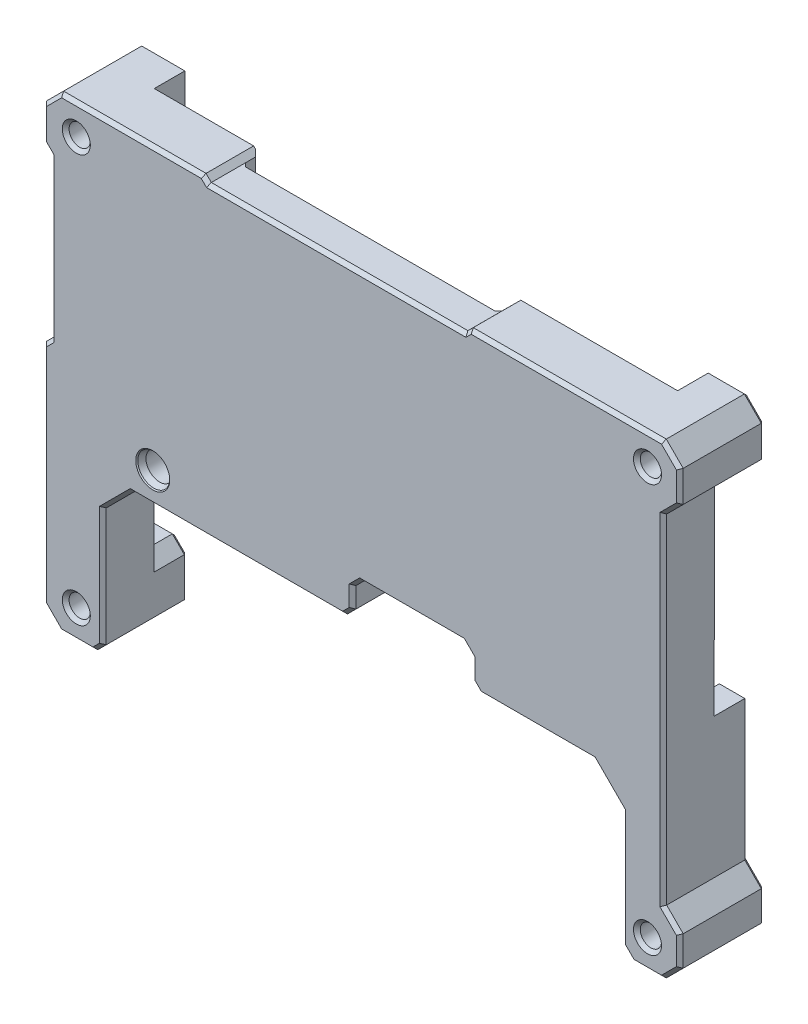
SolidWorks part; units mm, degrees
ref_plane "前视基准面" through (0, 0, 0) normal (0, 0, 1) x (1, 0, 0)
ref_plane "上视基准面" through (0, 0, 0) normal (0, 1, 0) x (1, 0, 0)
ref_plane "右视基准面" through (0, 0, 0) normal (1, 0, 0) x (0, 0, -1)
other "Configuration Table"
sketch "草图1" plane through (0, 0, 0) normal (0, 0, 1) x (1, 0, 0)
  line L1 (0, 0) -> (85, 0)
  line L2 (0, 0) -> (0, 65)
  line L3 (0, 65) -> (85, 65)
  line L4 (85, 0) -> (85, 65)
  dimension "D1" = 65
  dimension "D2" = 85
extrude "凸台-拉伸1" add sketch "草图1" along normal blind 10
sketch "草图2" plane through (0, 0, 0) normal (0, 0, -1) x (-1, 0, 0)
  circle A0 centre (-76.1669, 56.4425) radius 1.25
  circle A1 centre (-8.8888, 56.4425) radius 1.25
  circle A2 centre (-76.1669, 8.4151) radius 1.25
  circle A3 centre (-8.8888, 8.4151) radius 1.25
  dimension "D1" = 2.5
  dimension "D2" = 2.5
  dimension "D3" = 2.5
  dimension "D4" = 2.5
extrude "切除-拉伸1" cut sketch "草图2" against normal up to next
sketch "草图3" plane through (0, 0, 0) normal (0, 0, -1) x (-1, 0, 0)
  line L28 (-85, 0) -> (-85, 65) construction
  line L29 (-85, 65) -> (0, 65)
  line L30 (-85, 65) -> (-85, 0)
  line L31 (-85, 0) -> (0, 0)
  line L32 (0, 65) -> (0, 0)
  line L56 (-5, 33.4629) -> (-5.8713, 34.3342)
  line L57 (-5, 6.9926) -> (-5, 33.4629)
  line L58 (-6.9926, 5) -> (-5, 6.9926)
  line L59 (-16.2697, 5) -> (-6.9926, 5)
  line L60 (-17.4616, 6.1866) -> (-16.2697, 5)
  line L61 (-31.7436, 6.1829) -> (-17.4616, 6.1866)
  line L62 (-32.9265, 5) -> (-31.7436, 6.1829)
  line L63 (-58.7727, 5) -> (-32.9265, 5)
  line L64 (-60.0435, 6.2655) -> (-58.7727, 5)
  line L65 (-73.1524, 6.2618) -> (-60.0435, 6.2655)
  line L66 (-74.4142, 5) -> (-73.1524, 6.2618)
  line L67 (-77.9822, 5) -> (-74.4142, 5)
  line L68 (-79.9747, 6.9926) -> (-77.9822, 5)
  line L69 (-79.9747, 10.5083) -> (-79.9747, 6.9926)
  line L70 (-78.0283, 12.46) -> (-79.9747, 10.5083)
  line L71 (-78.032, 52.3531) -> (-78.0283, 12.46)
  line L72 (-79.9747, 54.2958) -> (-78.032, 52.3531)
  line L73 (-79.9747, 57.9821) -> (-79.9747, 54.2958)
  line L74 (-77.9822, 59.9747) -> (-79.9747, 57.9821)
  line L75 (-55.2451, 59.9747) -> (-77.9822, 59.9747)
  line L76 (-54.6148, 59.3497) -> (-55.2451, 59.9747)
  line L77 (-24.3949, 59.3534) -> (-54.6148, 59.3497)
  line L78 (-23.7736, 59.9747) -> (-24.3949, 59.3534)
  line L79 (-6.9926, 59.9747) -> (-23.7736, 59.9747)
  line L80 (-5, 57.9821) -> (-6.9926, 59.9747)
  line L81 (-5, 54.0174) -> (-5, 57.9821)
  line L82 (-5.875, 53.1371) -> (-5, 54.0174)
  line L83 (-5.8713, 34.3342) -> (-5.875, 53.1371)
extrude "切除-拉伸2" cut sketch "草图3" against normal up to next
sketch "草图4" plane through (0, 0, 0) normal (0, 0, -1) x (-1, 0, 0)
  line L0 (-73.1524, 6.2618) -> (-73.1524, 20.0323)
  line L1 (-73.1524, 20.0323) -> (-69.8316, 23.3532)
  line L2 (-69.8316, 23.3532) -> (-46.788, 23.3532)
  line L3 (-46.788, 23.3532) -> (-15.4038, 23.3532)
  line L4 (-15.4038, 23.3532) -> (-12.014, 19.9634)
  line L5 (-12.014, 19.9634) -> (-12.014, 6.188)
  line L6 (-31.7436, 6.1829) -> (-17.4616, 6.1866) construction
  line L7 (-12.014, 6.188) -> (-12.014, 0.194)
  line L8 (-12.014, 0.194) -> (-73.1524, 0.194)
  line L9 (-73.1524, 0.194) -> (-73.1524, 6.2618)
  line L10 (-73.1524, 6.2618) -> (-60.0435, 6.2655) construction
  dimension "D1" = 135
  dimension "D2" = 135
  dimension "D3" = 4.7938
extrude "切除-拉伸4" cut sketch "草图4" against normal up to next
sketch "草图5" plane through (0, 0, 0) normal (0, 0, -1) x (-1, 0, 0)
  line L0 (-24.3949, 59.3534) -> (-24.3949, 53.9064)
  line L1 (-24.3949, 53.9064) -> (-25.5261, 52.7749)
  line L2 (-25.5261, 52.7749) -> (-53.4826, 52.7749)
  line L3 (-53.4826, 52.7749) -> (-54.6142, 53.9061)
  line L4 (-54.6142, 53.9061) -> (-54.6148, 59.3497)
  line L5 (-24.3949, 59.3534) -> (-54.6148, 59.3497) construction
  line L6 (-23.7736, 59.9747) -> (-24.3949, 59.3534) construction
  line L7 (-24.3949, 59.3534) -> (-54.6148, 59.3497)
  dimension "D1" = 135
  dimension "D2" = 134.993
  dimension "D3" = 1.6
  dimension "D4" = 1.6
extrude "切除-拉伸7" cut sketch "草图5" against normal blind 6
sketch "草图6" plane through (0, 0, 0) normal (0, 0, -1) x (-1, 0, 0)
  line L0 (-5.8713, 34.3342) -> (-11.6713, 34.3342)
  line L1 (-5, 33.4629) -> (-5.8713, 34.3342) construction
  line L6 (-5.8713, 34.3342) -> (-5.875, 53.1371) construction
  line L7 (-5.8735, 45.2504) -> (-5.8745, 50.3342)
  line L8 (-5.8735, 45.2504) -> (-5.8713, 34.3342)
  line L9 (-5.8745, 50.3342) -> (-11.6713, 50.3342)
  line L10 (-11.6713, 50.3342) -> (-11.6713, 34.3342)
  dimension "D1" = 5.8
  dimension "D2" = 16
extrude "切除-拉伸8" cut sketch "草图6" against normal blind 6
sketch "草图7" plane through (0, 0, 0) normal (0, 0, -1) x (-1, 0, 0)
  line L0 (-76.4321, 51.2623) -> (-74.4321, 51.2623)
  line L1 (-74.4321, 51.2623) -> (-71.3195, 54.3749)
  line L2 (-71.3195, 54.3749) -> (-71.3195, 58.3749)
  line L3 (-71.3195, 58.3749) -> (-71.3195, 59.9747)
  line L4 (-76.4321, 51.2623) -> (-78.0319, 51.2623)
  line L5 (-78.0298, 28.9377) -> (-75.0298, 28.9377)
  line L6 (-75.0298, 28.9377) -> (-75.0298, 13.9377)
  line L7 (-72.9158, 11.8236) -> (-75.0298, 13.9377)
  line L8 (-24.3949, 57.6633) -> (-23.7321, 57.6633)
  line L9 (-23.7321, 57.6633) -> (-23.0617, 58.334)
  line L10 (-23.0617, 58.334) -> (-12.072, 58.334)
  line L11 (-12.072, 58.334) -> (-12.072, 55.334)
  line L12 (-12.072, 55.334) -> (-9.875, 53.1371)
  line L13 (-9.875, 53.1371) -> (-5.875, 53.1371)
  line L14 (-6.5998, 12.014) -> (-10.5998, 12.014)
  line L15 (-10.5998, 12.014) -> (-12.014, 10.5998)
  line L16 (-12.014, 10.5998) -> (-12.014, 5)
  line L17 (-6.5998, 12.014) -> (-5, 12.014)
  line L18 (-72.9158, 11.8236) -> (-73.1524, 12.0603)
  line L37 (-5.8713, 34.3342) -> (-11.6713, 34.3342)
  line L38 (-11.6713, 34.3342) -> (-11.6713, 50.3342)
  line L39 (-11.6713, 34.3342) -> (-11.6713, 50.3342)
  line L40 (-11.6713, 50.3342) -> (-5.8745, 50.3342)
  line L41 (-11.6713, 50.3342) -> (-5.8745, 50.3342)
  line L42 (-5.8745, 50.3342) -> (-5.875, 53.1371)
  line L43 (-5.875, 53.1371) -> (-5, 54.0174)
  line L44 (-5, 54.0174) -> (-5, 57.9821)
  line L45 (-5, 57.9821) -> (-6.9926, 59.9747)
  line L46 (-6.9926, 59.9747) -> (-23.7736, 59.9747)
  line L47 (-23.7736, 59.9747) -> (-24.3949, 59.3534)
  line L48 (-24.3949, 59.3534) -> (-24.3949, 53.9064)
  line L49 (-24.3949, 53.9064) -> (-25.5261, 52.7749)
  line L50 (-25.5261, 52.7749) -> (-53.4826, 52.7749)
  line L51 (-53.4826, 52.7749) -> (-54.6142, 53.9061)
  line L52 (-54.6142, 53.9061) -> (-54.6148, 59.3497)
  line L53 (-54.6148, 59.3497) -> (-55.2451, 59.9747)
  line L54 (-55.2451, 59.9747) -> (-77.9822, 59.9747)
  line L55 (-77.9822, 59.9747) -> (-79.9747, 57.9821)
  line L56 (-79.9747, 57.9821) -> (-79.9747, 54.2958)
  line L57 (-79.9747, 54.2958) -> (-78.032, 52.3531)
  line L58 (-78.032, 52.3531) -> (-78.0283, 12.46)
  line L59 (-78.0283, 12.46) -> (-79.9747, 10.5083)
  line L60 (-79.9747, 10.5083) -> (-79.9747, 6.9926)
  line L61 (-79.9747, 6.9926) -> (-77.9822, 5)
  line L62 (-77.9822, 5) -> (-74.4142, 5)
  line L63 (-74.4142, 5) -> (-73.1524, 6.2618)
  line L64 (-73.1524, 6.2618) -> (-73.1524, 20.0323)
  line L65 (-73.1524, 20.0323) -> (-69.8316, 23.3532)
  line L66 (-69.8316, 23.3532) -> (-15.4038, 23.3532)
  line L67 (-15.4038, 23.3532) -> (-12.014, 19.9634)
  line L68 (-12.014, 19.9634) -> (-12.014, 5)
  line L70 (-12.014, 5) -> (-6.9926, 5)
  line L71 (-6.9926, 5) -> (-5, 6.9926)
  line L72 (-5, 6.9926) -> (-5, 33.4629)
  line L73 (-5, 33.4629) -> (-5.8713, 34.3342)
  line L74 (-5.8713, 34.3342) -> (-11.6713, 34.3342)
  line L79 (-5.8745, 50.3342) -> (-5.875, 53.1371)
  line L80 (-5.875, 53.1371) -> (-5, 54.0174)
  line L81 (-5, 54.0174) -> (-5, 57.9821)
  line L82 (-5, 57.9821) -> (-6.9926, 59.9747)
  line L83 (-6.9926, 59.9747) -> (-23.7736, 59.9747)
  line L84 (-23.7736, 59.9747) -> (-24.3949, 59.3534)
  line L85 (-24.3949, 59.3534) -> (-24.3949, 53.9064)
  line L86 (-24.3949, 53.9064) -> (-25.5261, 52.7749)
  line L87 (-25.5261, 52.7749) -> (-53.4826, 52.7749)
  line L88 (-53.4826, 52.7749) -> (-54.6142, 53.9061)
  line L89 (-54.6142, 53.9061) -> (-54.6148, 59.3497)
  line L90 (-54.6148, 59.3497) -> (-55.2451, 59.9747)
  line L91 (-55.2451, 59.9747) -> (-77.9822, 59.9747)
  line L92 (-77.9822, 59.9747) -> (-79.9747, 57.9821)
  line L93 (-79.9747, 57.9821) -> (-79.9747, 54.2958)
  line L94 (-79.9747, 54.2958) -> (-78.032, 52.3531)
  line L95 (-78.032, 52.3531) -> (-78.0283, 12.46)
  line L96 (-78.0283, 12.46) -> (-79.9747, 10.5083)
  line L97 (-79.9747, 10.5083) -> (-79.9747, 6.9926)
  line L98 (-79.9747, 6.9926) -> (-77.9822, 5)
  line L99 (-77.9822, 5) -> (-74.4142, 5)
  line L100 (-74.4142, 5) -> (-73.1524, 6.2618)
  line L101 (-73.1524, 6.2618) -> (-73.1524, 20.0323)
  line L102 (-73.1524, 20.0323) -> (-69.8316, 23.3532)
  line L103 (-69.8316, 23.3532) -> (-15.4038, 23.3532)
  line L104 (-15.4038, 23.3532) -> (-12.014, 19.9634)
  line L105 (-12.014, 19.9634) -> (-12.014, 5)
  line L107 (-12.014, 5) -> (-6.9926, 5)
  line L108 (-6.9926, 5) -> (-5, 6.9926)
  line L109 (-5, 6.9926) -> (-5, 33.4629)
  line L110 (-5, 33.4629) -> (-5.8713, 34.3342)
  dimension "D2" = 90
  dimension "D3" = 15
  dimension "D4" = 135
  dimension "D5" = 4
  dimension "D6" = 3
  dimension "D7" = 135
  dimension "D8" = 45
  dimension "D9" = 3
  dimension "D1" = 0
extrude "切除-拉伸11" cut sketch "草图7" against normal blind 4
sketch "草图8" plane through (0, 0, 4) normal (0, 0, -1) x (-1, 0, 0)
  line L1 (-73.3481, 45.9587) -> (-65.3481, 45.9587)
  line L2 (-73.3481, 45.9587) -> (-73.3481, 40.9587)
  line L3 (-73.3481, 40.9587) -> (-65.3481, 40.9587)
  line L4 (-65.3481, 45.9587) -> (-65.3481, 40.9587)
  dimension "D1" = 5
  dimension "D2" = 8
extrude "切除-拉伸12" cut sketch "草图8" against normal blind 1
sketch "草图10" plane through (0, 0, 4) normal (0, 0, -1) x (-1, 0, 0)
  line L0 (-41.5465, 34.8898) -> (-37.5465, 34.8898)
  line L1 (-46.9465, 34.8898) -> (-41.5465, 34.8898)
  line L2 (-46.9465, 34.8898) -> (-46.9465, 28.8898)
  line L3 (-46.9465, 28.8898) -> (-41.5465, 28.8898)
  line L4 (-41.5465, 34.8898) -> (-41.5465, 28.8898)
  line L5 (-37.5465, 34.8898) -> (-32.1465, 34.8898)
  line L6 (-37.5465, 34.8898) -> (-37.5465, 28.8898)
  line L7 (-37.5465, 28.8898) -> (-32.1465, 28.8898)
  line L8 (-32.1465, 34.8898) -> (-32.1465, 28.8898)
  line L9 (-37.5465, 28.8898) -> (-41.5465, 28.8898)
  dimension "D1" = 5.4
  dimension "D2" = 6
  dimension "D3" = 5.4
  dimension "D4" = 4
extrude "凸台-拉伸2" add sketch "草图10" along normal offset from surface (2.04 mm away) 3 contours L4 L1 L2 L3 | L9 L6 L0 L4 | L8 L5 L6 L7
sketch "草图11" plane through (0, 0, 4) normal (0, 0, -1) x (-1, 0, 0)
  line L1 (-40.8318, 43.6929) -> (-36.6318, 43.6929)
  line L2 (-40.8318, 43.6929) -> (-40.8318, 38.6929)
  line L3 (-40.8318, 38.6929) -> (-36.6318, 38.6929)
  line L4 (-36.6318, 43.6929) -> (-36.6318, 38.6929)
  dimension "D1" = 4.2
  dimension "D2" = 5
extrude "凸台-拉伸3" add sketch "草图11" along normal offset from surface (1.3001 mm away) 3
sketch "草图12" plane through (0, 0, 4) normal (0, 0, -1) x (-1, 0, 0)
  line L0 (-24.6106, 30.6859) -> (-32.1465, 34.8898)
  line L1 (-30.6106, 30.6859) -> (-18.6106, 30.6859)
  line L2 (-30.6106, 30.6859) -> (-30.6106, 24.6859)
  line L3 (-30.6106, 24.6859) -> (-18.6106, 24.6859)
  line L4 (-18.6106, 30.6859) -> (-18.6106, 24.6859)
  line L5 (-32.1465, 34.8898) -> (-46.9465, 34.8898) construction
  line L6 (-32.1465, 28.8898) -> (-32.1465, 34.8898) construction
  line L7 (-32.1465, 34.8898) -> (-32.1465, 28.8898)
  line L8 (-32.1465, 28.8898) -> (-30.6106, 27.6859)
  line M47 (-32.1465, 34.8898) -> (-32.1465, 28.8898)
  dimension "D1" = 12
  dimension "D2" = 6
extrude "凸台-拉伸4" add sketch "草图12" along normal offset from surface (1.89 mm away) 3 contours L4 L1 L2 L3 | L8 L2 L1 L0 M47
sketch "草图13" plane through (0, 0, 4) normal (0, 0, -1) x (-1, 0, 0)
  line L1 (-62.8902, 40.6188) -> (-59.7758, 40.6188)
  line L2 (-62.8902, 40.6188) -> (-62.8902, 35.6362)
  line L3 (-62.8902, 35.6362) -> (-59.7758, 35.6362)
  line L4 (-59.7758, 40.6188) -> (-59.7758, 35.6362)
extrude "凸台-拉伸5" add sketch "草图13" along normal offset from surface (4 mm away) 2
sketch "草图15" plane through (0, 0, 10) normal (0, 0, 1) x (1, 0, 0)
  line L0 (69.8316, 23.3532) -> (15.4038, 23.3532) construction
  line L1 (41.4288, 23.3532) -> (55.4288, 23.3532)
  line L2 (41.4288, 23.3532) -> (41.4288, 27.7532)
  line L3 (41.4288, 27.7532) -> (55.4288, 27.7532)
  line L4 (55.4288, 23.3532) -> (55.4288, 27.7532)
  dimension "D1" = 14
  dimension "D2" = 4.4
extrude "切除-拉伸13" cut sketch "草图15" against normal up to surface (6 mm away) up to face at (69.3481, 43.4587, 4)
chamfer "倒角1" distance 1 angle 45 5 edges at (12.014, 5, 5) (55.4288, 23.3532, 7) (55.4288, 27.7532, 7) (41.4288, 27.7532, 7) (41.4288, 23.3532, 7)
chamfer "倒角2" distance 0.6 angle 45 4 edges at (59.7758, 38.1275, 4) (61.333, 40.6188, 4) (62.8902, 38.1275, 4) (61.333, 35.6362, 4)
chamfer "倒角5" distance 0.6 angle 45 4 edges at (36.6318, 41.1929, 4) (38.7318, 38.6929, 4) (40.8318, 41.1929, 4) (38.7318, 43.6929, 4)
sketch "草图16" plane through (0, 0, 4) normal (0, 0, -1) x (-1, 0, 0)
  circle A0 centre (-17.8941, 26.9463) radius 1.6
  dimension "D1" = 3.2
extrude "切除-拉伸14" cut sketch "草图16" against normal through all both and the other way through all
sketch "草图17" plane through (0, 0, 0) normal (0, 0, -1) x (-1, 0, 0)
  line L0 (-12.072, 58.334) -> (-12.072, 59.9747)
  line L2 (-6.9926, 59.9747) -> (-23.7736, 59.9747) construction
  line L15 (-24.3949, 59.3534) -> (-24.3949, 57.6633)
  line L16 (-24.3949, 57.6633) -> (-23.7321, 57.6633)
  line L17 (-23.7321, 57.6633) -> (-23.0617, 58.334)
  line L18 (-23.0617, 58.334) -> (-12.072, 58.334)
  line L19 (-12.072, 58.334) -> (-12.072, 55.334)
  line L20 (-12.072, 55.334) -> (-9.875, 53.1371)
  line L21 (-9.875, 53.1371) -> (-5.875, 53.1371)
  line L22 (-5.875, 53.1371) -> (-5, 54.0174)
  line L23 (-5, 54.0174) -> (-5, 57.9821)
  line L24 (-5, 57.9821) -> (-6.9926, 59.9747)
  line L25 (-6.9926, 59.9747) -> (-23.7736, 59.9747)
  line L26 (-23.7736, 59.9747) -> (-24.3949, 59.3534)
  line L27 (-24.3949, 59.3534) -> (-24.3949, 57.6633)
  line L28 (-24.3949, 57.6633) -> (-23.7321, 57.6633)
  line L29 (-23.7321, 57.6633) -> (-23.0617, 58.334)
  line L30 (-23.0617, 58.334) -> (-12.072, 58.334)
  line L31 (-12.072, 58.334) -> (-12.072, 55.334)
  line L32 (-12.072, 55.334) -> (-9.875, 53.1371)
  line L33 (-9.875, 53.1371) -> (-5.875, 53.1371)
  line L34 (-5.875, 53.1371) -> (-5, 54.0174)
  line L35 (-5, 54.0174) -> (-5, 57.9821)
  line L36 (-5, 57.9821) -> (-6.9926, 59.9747)
  line L37 (-6.9926, 59.9747) -> (-23.7736, 59.9747)
  line L38 (-23.7736, 59.9747) -> (-24.3949, 59.3534)
  line M15 (-24.3949, 59.3534) -> (-24.3949, 57.6633)
  line M16 (-24.3949, 57.6633) -> (-23.7321, 57.6633)
  line M17 (-23.7321, 57.6633) -> (-23.0617, 58.334)
  line M18 (-23.0617, 58.334) -> (-12.072, 58.334)
  line M25 (-6.9926, 59.9747) -> (-23.7736, 59.9747)
  line M26 (-23.7736, 59.9747) -> (-24.3949, 59.3534)
  dimension "D1" = 0
extrude "切除-拉伸15" cut sketch "草图17" against normal up to surface (4 mm away) contours L0 M18 M25 M26 M15 M16 M17 up to face at (28.7404, 29.0801, 4)
sketch "草图18" plane through (0, 0, 0) normal (0, 0, -1) x (-1, 0, 0)
  line L0 (-73.7195, 59.9747) -> (-73.7195, 54.0502)
  line L1 (-71.3195, 59.9747) -> (-77.9822, 59.9747) construction
  line L2 (-73.7195, 54.0502) -> (-75.4166, 52.3531)
  line L3 (-75.4166, 52.3531) -> (-78.032, 52.3531)
  line L12 (-78.032, 52.3531) -> (-78.0319, 51.2623)
  line L13 (-78.0319, 51.2623) -> (-74.4321, 51.2623)
  line L14 (-74.4321, 51.2623) -> (-71.3195, 54.3749)
  line L15 (-71.3195, 54.3749) -> (-71.3195, 59.9747)
  line L16 (-71.3195, 59.9747) -> (-77.9822, 59.9747)
  line L17 (-77.9822, 59.9747) -> (-79.9747, 57.9821)
  line L18 (-79.9747, 57.9821) -> (-79.9747, 54.2958)
  line L19 (-79.9747, 54.2958) -> (-78.032, 52.3531)
  line L20 (-78.032, 52.3531) -> (-78.0319, 51.2623)
  line L21 (-78.0319, 51.2623) -> (-74.4321, 51.2623)
  line L22 (-74.4321, 51.2623) -> (-71.3195, 54.3749)
  line L23 (-71.3195, 54.3749) -> (-71.3195, 59.9747)
  line L24 (-71.3195, 59.9747) -> (-77.9822, 59.9747)
  line L25 (-77.9822, 59.9747) -> (-79.9747, 57.9821)
  line L26 (-79.9747, 57.9821) -> (-79.9747, 54.2958)
  line L27 (-79.9747, 54.2958) -> (-78.032, 52.3531)
  line M13 (-78.032, 52.3531) -> (-78.0319, 51.2623)
  line M14 (-78.0319, 51.2623) -> (-74.4321, 51.2623)
  line M15 (-74.4321, 51.2623) -> (-71.3195, 54.3749)
  line M16 (-71.3195, 54.3749) -> (-71.3195, 59.9747)
  line M17 (-71.3195, 59.9747) -> (-77.9822, 59.9747)
  dimension "D1" = 0
  dimension "D2" = 2.4
  dimension "D3" = 2.4
extrude "切除-拉伸16" cut sketch "草图18" against normal up to surface (4 mm away) contours L2 L3 L0 M13 M14 M15 M16 M17 up to face at (28.7404, 29.0801, 4)
chamfer "倒角6" distance 0.4 angle 45 40 edges at (5.9963, 5.9963, 10) (5, 20.2277, 10) (5.4357, 33.8986, 10) (5.8732, 43.7356, 10) (5.4375, 53.5772, 10) (5, 55.9998, 10) (5.9963, 58.9784, 10) (15.3831, 59.9747, 10) (24.0842, 59.6641, 10) (39.5048, 59.3515, 10) (54.93, 59.6622, 10) (66.6136, 59.9747, 10) (78.9785, 58.9784, 10) (79.9747, 56.139, 10) (79.0034, 53.3245, 10) (78.0302, 32.4066, 10) (79.0015, 11.4841, 10) (79.9747, 8.7504, 10) (78.9785, 5.9963, 10) (76.1982, 5, 10) (73.7833, 5.6309, 10) (73.1524, 13.1471, 10) (71.492, 21.6927, 10) (27.9163, 23.3532, 10) (55.9288, 23.8532, 10) (55.4288, 25.5532, 10) (54.9288, 27.2532, 10) (48.4288, 27.7532, 10) (41.9288, 27.2532, 10) (41.4288, 25.5532, 10) (40.9288, 23.8532, 10) (13.7089, 21.6583, 10) (12.014, 12.9817, 10) (11.514, 5.5, 10) (9.0033, 5, 10) (7.6388, 56.4425, 10) (74.9169, 8.4151, 10) (7.6388, 8.4151, 10) (74.9169, 56.4425, 10) (16.2941, 26.9463, 10)
chamfer "倒角7" distance 0.4 angle 45 43 edges at (59.7758, 38.1275, 0) (61.333, 35.6362, 0) (62.8902, 38.1275, 0) (61.333, 40.6188, 0) (40.8318, 41.1929, 2.6999) (38.7318, 43.6929, 2.6999) (36.6318, 41.1929, 2.6999) (38.7318, 38.6929, 2.6999) (74.9169, 56.4425, 0) (74.568, 53.2016, 0) (76.7243, 52.3531, 0) (79.0034, 53.3245, 0) (79.9747, 56.139, 0) (78.9785, 58.9784, 0) (75.8509, 59.9747, 0) (73.7195, 57.0124, 0) (73.7833, 5.6309, 0) (76.1982, 5, 0) (78.9785, 5.9963, 0) (79.9747, 8.7504, 0) (79.0015, 11.4841, 0) (78.0291, 20.6989, 0) (76.5298, 28.9377, 0) (75.0298, 21.4377, 0) (74.0911, 12.999, 0) (73.1524, 9.1611, 0) (74.9169, 8.4151, 0) (11.3069, 11.3069, 0) (7.7999, 12.014, 0) (5, 9.5033, 0) (5.9963, 5.9963, 0) (9.0033, 5, 0) (11.514, 5.5, 0) (12.014, 8.2999, 0) (7.6388, 8.4151, 0) (7.6388, 56.4425, 0) (5.9963, 58.9784, 0) (5, 55.9998, 0) (5.4375, 53.5772, 0) (7.875, 53.1371, 0) (10.9735, 54.2355, 0) (12.072, 57.6543, 0) (9.5323, 59.9747, 0)
chamfer "倒角8" distance 0.4 angle 45 8 edges at (8.7729, 50.3342, 6) (11.6713, 50.3342, 5) (11.6713, 42.3342, 6) (8.7713, 34.3342, 6) (11.6713, 34.3342, 5) (8.7729, 50.3342, 4) (11.6713, 42.3342, 4) (8.7713, 34.3342, 4)
chamfer "倒角9" distance 0.4 angle 45 10 edges at (54.6145, 56.6279, 4) (54.6145, 56.6279, 6) (54.0484, 53.3405, 4) (54.0484, 53.3405, 6) (24.3949, 56.6299, 4) (24.3949, 56.6299, 6) (24.9605, 53.3407, 4) (24.9605, 53.3407, 6) (39.5044, 52.7749, 4) (39.5044, 52.7749, 6)
chamfer "倒角11" distance 0.4 angle 45 4 edges at (69.3481, 45.9587, 5) (65.3481, 43.4587, 5) (69.3481, 40.9587, 5) (73.3481, 43.4587, 5)
sketch "草图19" plane through (0, 0, 4) normal (0, 0, -1) x (-1, 0, 0)
  line L1 (-67.6316, 31.7532) -> (-58.2316, 31.7532)
  line L2 (-67.6316, 31.7532) -> (-67.6316, 23.3532)
  line L3 (-67.6316, 23.3532) -> (-58.2316, 23.3532)
  line L4 (-58.2316, 31.7532) -> (-58.2316, 23.3532)
  line L5 (-69.8316, 23.3532) -> (-56.4288, 23.3532) construction
  point P4 (0, 0)
  point P5 (0, 0)
  point P7 (0, 0)
  point P9 (-56.5482, 17.3287)
  dimension "D1" = 9.4
  dimension "D2" = 8.4
  dimension "D3" = 2.2
extrude "切除-拉伸17" cut sketch "草图19" against normal blind 2.4
chamfer "倒角12" distance 0.4 angle 45 11 edges at (67.6316, 27.5532, 6.4) (67.6316, 23.3532, 5.2) (62.9316, 31.7532, 6.4) (67.6316, 31.7532, 5.2) (58.2316, 27.5532, 6.4) (58.2316, 31.7532, 5.2) (62.9316, 23.3532, 6.4) (58.2316, 23.3532, 5.2) (67.6316, 27.5532, 4) (58.2316, 27.5532, 4) (62.9316, 31.7532, 4)
chamfer "倒角13" distance 0.4 5 edges at (19.4941, 26.9463, 2.11) (16.2941, 26.9463, 4) (18.6106, 28.3769, 3.055) (18.6106, 25.5156, 3.055) (16.2941, 26.9463, 9.6)
